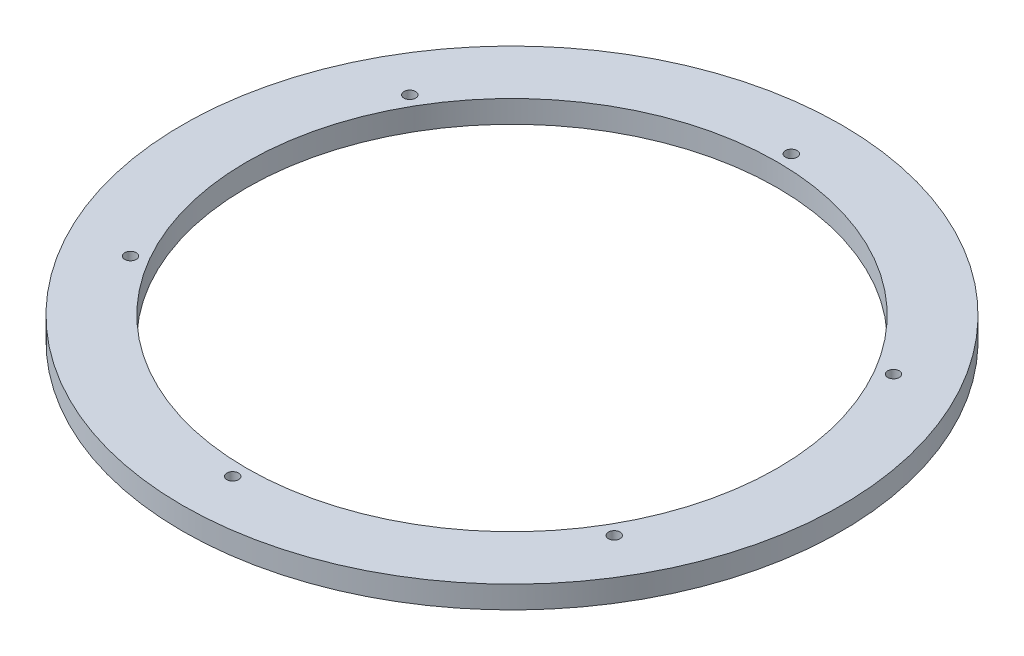
SolidWorks part; units mm, degrees
material "6061 Alloy"
ref_plane "Front Plane" through (0, 0, 0) normal (0, 0, 1) x (1, 0, 0)
ref_plane "Top Plane" through (0, 0, 0) normal (0, 1, 0) x (1, 0, 0)
ref_plane "Right Plane" through (0, 0, 0) normal (1, 0, 0) x (0, 0, -1)
sketch "Sketch1" plane through (0, 0, 0) normal (0, 1, 0) x (1, 0, 0)
  circle A0 centre (0, 0) radius 60.325
  circle A1 centre (0, 0) radius 74.93
  circle A2 centre (0, 0) radius 71.755
  circle A3 centre (0, -63.5) radius 1.3208
  circle A4 centre (-54.9926, -31.75) radius 1.3208
  circle A5 centre (-54.9926, 31.75) radius 1.3208
  circle A6 centre (0, 63.5) radius 1.3208
  circle A7 centre (54.9926, 31.75) radius 1.3208
  circle A8 centre (54.9926, -31.75) radius 1.3208
  point P21 (0, 0)
  dimension "D1" = 120.65
  dimension "D4" = 2.6416
  dimension "D5" = 63.5
  dimension "D2" = 14.605
  dimension "D3" = 11.43
  dimension "D6" = 6
extrude "Boss-Extrude1" add sketch "Sketch1" along normal blind 5.08 contours A2 A0 | A1 A2 region at (-72.8107, 0, 0) region at (-69.7255, 0, 0)
sketch "Sketch2" plane through (0, 0, 0) normal (1, 0, 0) x (0, 0, -1)
  line L0 (-74.93, 0) -> (74.93, 0) construction
  line L1 (74.93, 5.08) -> (-74.93, 5.08) construction
  line L2 (-74.93, 0) -> (74.93, 0)
  line L3 (74.93, 5.08) -> (-74.93, 5.08)
  line L4 (89.5975, 4.318) -> (99.9841, 4.318) construction
  line L5 (95.9885, 2.54) -> (99.6739, 2.54) construction
  line L6 (0, 0) -> (0, 18.217) construction
  circle A0 centre (71.755, 5.9055) radius 1.5875 construction
  circle A1 centre (71.755, 5.969) radius 1.651
  circle A2 centre (71.755, -0.889) radius 1.651
  dimension "D3" = 3.175
  dimension "D4" = 3.302
  dimension "D1" = 71.755
  dimension "D2" = 0.762
  dimension "D5" = 2.54
equation "\"Middle Coupler Inner Daimeter\"= 4.75in"
equation "\"Middle Coupler  Wall Thickness\" = 0.25in"
equation "\"Middle Coupler Bottom Thickness\"= 0.2in"
equation "\"Bearing Rail Offset\"= 0.45in"
equation "\"3-56 UNF Tap\"= 0.089in"
equation "\"3-56 UNF Clearance\"= 0.104in"
equation "\"D5@Sketch1\"=(\"Middle Coupler Inner Daimeter\"*2+0.5)/4in"
equation "\"Ball Bearing Distance\"= 0.03in"
equation "\"D1@Sketch2\"=\"Middle Coupler Inner Daimeter\"/2+\"Bearing Rail Offset\""
equation "\"D3@Sketch1\"=\"Bearing Rail Offset\""
equation "\"D4@Sketch1\"=\"3-56 UNF Clearance\""
equation "\"D1@Sketch1\"=\"Middle Coupler Inner Daimeter\""
equation "\"D2@Sketch2\"=\"Ball Bearing Distance\""
equation "\"D4@Sketch2\"=\"D3@Sketch2\"+0.005"
equation "\"D5@Sketch2\"=\"Middle Coupler Bottom Thickness\"/2"
equation "\"TCA Outer Diameter\" = 6.625in"
equation "\"Interstage Aeroframe Wall Thickness\" = 0.072in"
equation "\"Compression Spring OD\"= 0.42in"
equation "\"10-24 Tap\"= 0.157in"
equation "\"10-24 Clearance\"= 0.196in"
equation "\"Lower Stage Fuselage Wall Thickness\" = 0.25in"
equation "\"6-32 Tap\" = 0.107in"
equation "\"1/4-20 Tap\" = 0.201in"
